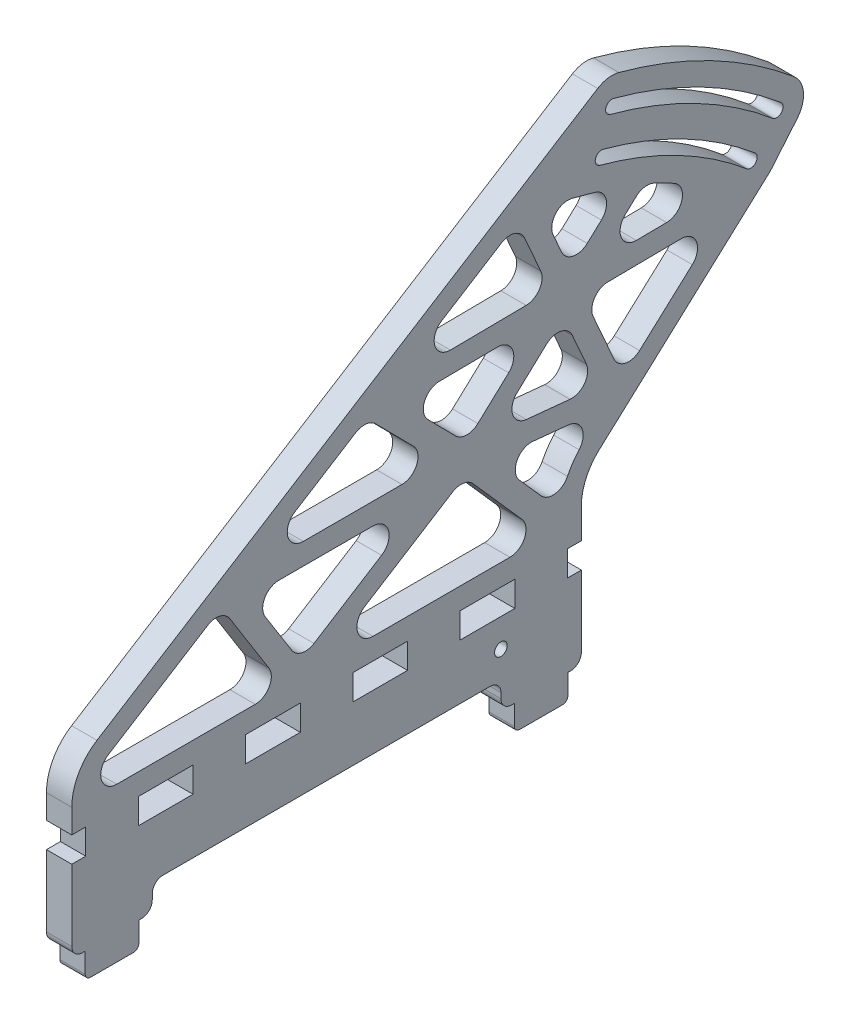
SolidWorks part; units mm, degrees
ref_plane "Front Plane" through (0, 0, 0) normal (0, 0, 1) x (1, 0, 0)
ref_plane "Top Plane" through (0, 0, 0) normal (0, 1, 0) x (1, 0, 0)
ref_plane "Right Plane" through (0, 0, 0) normal (1, 0, 0) x (0, 0, -1)
sketch "DriveBaseGeo"
  dimension "D1" = 6
  dimension "D2" = 6
  dimension "D5" = 203.2
  dimension "D8" = 25.4
  dimension "D9" = 25.4
  dimension "D6" = 9
  dimension "D7" = 9
sketch_block_instance "SlotOutline-1"
sketch_block "SlotOutline" parameters "D1"=12.7, "D2"=6
sketch_block_instance "SlotOutline-2"
sketch_block_instance "SlotOutline-3"
sketch_block_instance "SlotOutline-4"
sketch_block_instance "SlotOutline-5"
sketch_block_instance "SlotOutline-6"
sketch_block_instance "SlotOutline-7"
sketch_block_instance "SlotOutline-8"
sketch_block_instance "SlotOutline-9"
sketch_block_instance "SlotOutline-10"
sketch_block_instance "SlotOutline-11"
sketch_block_instance "SlotOutline-12"
sketch_block_instance "SlotOutline-13"
sketch_block_instance "SlotOutline-14"
sketch_block_instance "SlotOutline-15"
sketch_block_instance "SlotOutline-16"
sketch_block_instance "SlotOutline-17"
sketch_block_instance "SlotOutline-18"
sketch "Sketch2" plane through (0, 0, 0) normal (1, 0, 0) x (0, 0, -1)
  line L0 (-60.325, -47.8) -> (-60.325, -9.7)
  line L1 (-60.325, -9.7) -> (60.325, -9.7)
  line L2 (60.325, -9.7) -> (60.325, -47.8)
  line L3 (60.325, -47.8) -> (57.15, -47.8)
  line L4 (57.15, -47.8) -> (57.15, -53.8) construction
  line L5 (57.15, -53.8) -> (44.45, -53.8) construction
  line L6 (44.45, -53.8) -> (44.45, -47.8) construction
  line L7 (44.45, -47.8) -> (41.275, -47.8)
  line L8 (41.275, -47.8) -> (41.275, -41.45)
  line L9 (41.275, -41.45) -> (-41.275, -41.45)
  line L10 (-41.275, -41.45) -> (-41.275, -47.8)
  line L11 (-41.275, -47.8) -> (-44.45, -47.8)
  line L12 (-44.45, -47.8) -> (-44.45, -53.8) construction
  line L13 (-44.45, -53.8) -> (-57.15, -53.8) construction
  line L14 (-57.15, -53.8) -> (-57.15, -47.8) construction
  line L15 (-57.15, -47.8) -> (-60.325, -47.8)
  line L16 (-57.15, -47.8) -> (-44.45, -53.8) construction
  line L17 (44.45, -47.8) -> (57.15, -53.8) construction
  line L18 (57.15, -47.8) -> (44.45, -53.8) construction
  line L19 (-44.45, -47.8) -> (-57.15, -53.8) construction
  line L20 (101.6, -47.8) -> (-101.6, -47.8) construction
  line L21 (-41.275, -41.45) -> (-60.325, -41.45) construction
  line L22 (41.275, -41.45) -> (60.325, -41.45) construction
  line L23 (-60.325, -50.8) -> (-50.8, -50.8) construction
  line L24 (50.8, -50.8) -> (60.325, -50.8) construction
  line L25 (-57.15, -47.8) -> (-44.45, -47.8)
  line L26 (44.45, -47.8) -> (57.15, -47.8)
  line L27 (101.6, -22.4) -> (-101.6, -22.4) construction
  point P2 (50.8, -50.8)
  point P17 (-50.8, -50.8)
  dimension "D1" = 6.35
  dimension "D2" = 19.05
  dimension "D3" = 101.6
  dimension "D4" = 12.7
  dimension "D5" = 12.7
  dimension "D6" = 6
  dimension "D7" = 9.525
  dimension "D8" = 12.7
extrude "Mounting" add sketch "Sketch2" along normal mid plane 6
sketch "Sketch3" plane through (3, 0, 0) normal (1, 0, 0) x (0, 0, -1)
  line L0 (41.275, -35.1) -> (106.5822, 42.7301) construction
  line L3 (67.571, 63.0381) -> (41.275, -35.1) construction
  line L4 (41.275, -35.1) -> (160.1541, -35.1) construction
  line L6 (101.6, -47.8) -> (-101.6, -47.8) construction
  line L7 (60.325, -9.7) -> (60.325, -47.8) construction
  line L8 (64.1965, 68.4172) -> (-60.325, -9.7)
  line L9 (-60.325, -9.7) -> (60.325, -9.7)
  line L10 (111.4466, 38.6484) -> (105.3241, 31.3518)
  line L11 (105.3241, 31.3518) -> (100.4597, 35.4335) construction
  line L12 (104.7349, 30.7384) -> (60.325, -9.7)
  arc A0 (110.6639, 47.5945) -> (69.2145, 69.1717) centre (41.275, -35.1) ccw
  arc A1 (106.5822, 42.7301) -> (67.571, 63.0381) centre (41.275, -35.1) ccw construction
  arc A2 (107.5464, 43.8792) -> (67.9592, 64.487) centre (41.275, -35.1) ccw
  arc A3 (105.618, 41.581) -> (67.1828, 61.5892) centre (41.275, -35.1) ccw
  arc A4 (105.618, 41.581) -> (107.5464, 43.8792) centre (106.5822, 42.7301) ccw
  arc A5 (67.9592, 64.487) -> (67.1828, 61.5892) centre (67.571, 63.0381) ccw
  arc A6 (110.6639, 47.5945) -> (111.4466, 38.6484) centre (106.5822, 42.7301) cw
  arc A7 (69.2145, 69.1717) -> (64.1965, 68.4172) centre (67.571, 63.0381) ccw
  circle A8 centre (41.275, -35.1) radius 1.5
  arc A9 (100.4597, 35.4335) -> (65.1058, 53.8376) centre (41.275, -35.1) ccw construction
  arc A10 (101.4239, 36.5826) -> (65.494, 55.2865) centre (41.275, -35.1) ccw
  arc A11 (99.4955, 34.2845) -> (64.7175, 52.3887) centre (41.275, -35.1) ccw
  arc A12 (99.4955, 34.2845) -> (101.4239, 36.5826) centre (100.4597, 35.4335) ccw
  arc A13 (65.494, 55.2865) -> (64.7175, 52.3887) centre (65.1058, 53.8376) ccw
  arc A14 (105.3241, 31.3518) -> (104.7349, 30.7384) centre (100.4597, 35.4335) cw
  point P5 (88.1887, 55.0203)
  point P21 (41.275, -35.1)
  point P27 (83.7905, 46.5715)
  dimension "D1" = 3
  dimension "D4" = 6.35
  dimension "D8" = 3
  dimension "D2" = 25
  dimension "D3" = 50
  dimension "D5" = 101.6
  dimension "D6" = 12.7
  dimension "D7" = 19.05
  dimension "D9" = 9.525
extrude "Boss-Extrude2" add sketch "Sketch3" against normal up to surface (6 mm away) up to face at (-3, -36.6875, 0)
extrude "PivotHole" cut sketch "Sketch3<2>" against normal through all both and the other way through all contours A8 region at (3, -35.1, -41.275)
sketch "Sketch3<2>" plane through (3, 0, 0) normal (1, 0, 0) x (0, 0, -1) same geometry as "Sketch3"
sketch "Sketch4" plane through (0, -47.8, 0) normal (0, -1, 0) x (1, 0, 0)
  line L0 (-3, -41.275) -> (-3, -60.325) construction
  line L1 (-3, -60.325) -> (3, -60.325) construction
  line L2 (3, -60.325) -> (3, -41.275) construction
  line L3 (3, -41.275) -> (-3, -41.275) construction
  line L4 (-3, 60.325) -> (-3, 41.275) construction
  line L5 (-3, 41.275) -> (3, 41.275) construction
  line L6 (3, 41.275) -> (3, 60.325) construction
  line L7 (3, 60.325) -> (-3, 60.325) construction
  line L8 (-3, -41.275) -> (-3, -60.325) construction
  line L9 (-3, -60.325) -> (3, -60.325) construction
  line L10 (3, -60.325) -> (3, -41.275) construction
  line L11 (3, -41.275) -> (-3, -41.275) construction
  line L12 (-3, 60.325) -> (-3, 41.275) construction
  line L13 (-3, 41.275) -> (3, 41.275) construction
  line L14 (3, 41.275) -> (3, 60.325) construction
  line L15 (3, 60.325) -> (-3, 60.325) construction
  line L16 (-3, 60.325) -> (3, 41.275) construction
  line L17 (3, 60.325) -> (-3, 41.275) construction
  line L18 (-3, -41.275) -> (3, -60.325) construction
  line L19 (3, -41.275) -> (-3, -60.325) construction
  line L21 (-3, 44.45) -> (3, 44.45)
  line L22 (-3, 44.45) -> (-3, 57.15)
  line L23 (-3, 57.15) -> (3, 57.15)
  line L24 (3, 44.45) -> (3, 57.15)
  line L25 (-3, 44.45) -> (3, 57.15) construction
  line L26 (-3, 57.15) -> (3, 44.45) construction
  line L27 (-3, -57.15) -> (3, -57.15)
  line L28 (-3, -57.15) -> (-3, -44.45)
  line L29 (-3, -44.45) -> (3, -44.45)
  line L30 (3, -57.15) -> (3, -44.45)
  line L31 (-3, -57.15) -> (3, -44.45) construction
  line L32 (-3, -44.45) -> (3, -57.15) construction
  point P6 (0, -50.8)
  point P9 (0, 50.8)
  point P10 (0, 50.8)
  point P15 (0, -50.8)
  dimension "D1" = 12.7
extrude "Tab" add sketch "Sketch4" along normal blind 6
fillet "Fillet1" radius 12.7 2 edges at (0, -9.7, 60.325) (0, -9.7, -60.325)
fillet "Fillet2" radius 2.54 6 edges at (0, -47.8, -60.325) (0, -47.8, -41.275) (0, -41.45, 41.275) (0, -47.8, 41.275) (0, -47.8, 60.325) (0, -41.45, -41.275)
fillet "TabFillet" radius 1.27 4 edges at (0, -53.8, -57.15) (0, -53.8, -44.45) (0, -53.8, 44.45) (0, -53.8, 57.15)
sketch "Sketch5" plane through (3, 0, 0) normal (1, 0, 0) x (0, 0, -1)
  line L0 (101.6, -22.4) -> (-101.6, -22.4) construction
  line L1 (-82.423, -28.4) -> (-95.377, -28.4)
  line L2 (-82.423, -28.4) -> (-82.423, -22.4)
  line L3 (-82.423, -22.4) -> (-95.377, -22.4)
  line L4 (-95.377, -28.4) -> (-95.377, -22.4)
  line L5 (-82.423, -28.4) -> (-95.377, -22.4) construction
  line L6 (-82.423, -22.4) -> (-95.377, -28.4) construction
  line L7 (101.6, -28.4) -> (-101.6, -28.4) construction
  line L8 (-95.25, -28.4) -> (-82.55, -22.4) construction
  line L9 (-57.023, -28.4) -> (-69.977, -28.4)
  line L10 (-57.023, -28.4) -> (-57.023, -22.4)
  line L11 (-69.977, -28.4) -> (-69.977, -22.4)
  line L12 (-57.023, -28.4) -> (-69.977, -22.4) construction
  line L13 (-57.023, -22.4) -> (-69.977, -28.4) construction
  line L14 (-57.023, -22.4) -> (-69.977, -22.4)
  line L15 (-31.623, -28.4) -> (-44.577, -28.4)
  line L16 (-31.623, -28.4) -> (-31.623, -22.4)
  line L17 (-44.577, -28.4) -> (-44.577, -22.4)
  line L18 (-31.623, -28.4) -> (-44.577, -22.4) construction
  line L19 (-31.623, -22.4) -> (-44.577, -28.4) construction
  line L20 (-31.623, -22.4) -> (-44.577, -22.4)
  line L21 (-6.223, -28.4) -> (-19.177, -28.4)
  line L22 (-6.223, -28.4) -> (-6.223, -22.4)
  line L23 (-19.177, -28.4) -> (-19.177, -22.4)
  line L24 (-6.223, -28.4) -> (-19.177, -22.4) construction
  line L25 (-6.223, -22.4) -> (-19.177, -28.4) construction
  line L26 (-6.223, -22.4) -> (-19.177, -22.4)
  line L27 (19.177, -28.4) -> (6.223, -28.4)
  line L28 (19.177, -28.4) -> (19.177, -22.4)
  line L29 (6.223, -28.4) -> (6.223, -22.4)
  line L30 (19.177, -28.4) -> (6.223, -22.4) construction
  line L31 (19.177, -22.4) -> (6.223, -28.4) construction
  line L32 (19.177, -22.4) -> (6.223, -22.4)
  line L33 (44.577, -28.4) -> (31.623, -28.4)
  line L34 (44.577, -28.4) -> (44.577, -22.4)
  line L35 (31.623, -28.4) -> (31.623, -22.4)
  line L36 (44.577, -28.4) -> (31.623, -22.4) construction
  line L37 (44.577, -22.4) -> (31.623, -28.4) construction
  line L38 (44.577, -22.4) -> (31.623, -22.4)
  line L39 (69.977, -28.4) -> (57.023, -28.4)
  line L40 (69.977, -28.4) -> (69.977, -22.4)
  line L41 (57.023, -28.4) -> (57.023, -22.4)
  line L42 (69.977, -28.4) -> (57.023, -22.4) construction
  line L43 (69.977, -22.4) -> (57.023, -28.4) construction
  line L44 (69.977, -22.4) -> (57.023, -22.4)
  line L45 (95.377, -28.4) -> (82.423, -28.4)
  line L46 (95.377, -28.4) -> (95.377, -22.4)
  line L47 (82.423, -28.4) -> (82.423, -22.4)
  line L48 (95.377, -28.4) -> (82.423, -22.4) construction
  line L49 (95.377, -22.4) -> (82.423, -28.4) construction
  line L50 (95.377, -22.4) -> (82.423, -22.4)
  point P0 (-88.9, -25.4)
  point P18 (-63.5, -25.4)
  dimension "D2" = 25.4
  dimension "D3" = 12.446
  dimension "D1" = 8
extrude "Cut-Extrude2" cut sketch "Sketch5" against normal through all both and the other way through all
sketch "Sketch7" plane through (3, 0, 0) normal (1, 0, 0) x (0, 0, -1)
  line L0 (33.0261, 7.8463) -> (72.5595, 44.4656) construction
  line L1 (68.2118, 4.352) -> (47.2733, 51.8037) construction
  line L2 (11.6881, 29.4797) -> (96.2301, 30.393) construction
  line L3 (-24.948, 6.4965) -> (-7.8091, -20.8234)
  line L4 (-7.8091, -20.8234) -> (34.3778, 5.6959)
  line L5 (34.8344, 9.63) -> (17.6972, 27.0045)
  line L6 (17.6972, 27.0045) -> (96.2576, 27.8531)
  line L7 (31.122, 6.1652) -> (53.3409, -19.0011)
  line L8 (64.1304, 7.3098) -> (44.9494, 50.7783)
  line L9 (64.1304, 7.3098) -> (33.2771, 10.3739)
  line L10 (35.0518, 6.2605) -> (76.5725, 44.7206)
  line L11 (-20.6447, 9.1961) -> (-6.2079, -13.8166)
  line L12 (-6.2079, -13.8166) -> (31.6743, 9.9967)
  line L13 (31.2177, 6.0627) -> (5.679, 31.955)
  line L14 (5.679, 31.955) -> (96.2027, 32.9328)
  line L15 (34.9302, 9.5274) -> (57.1491, -15.6389)
  line L16 (72.2933, 1.3942) -> (49.5971, 52.8291)
  line L17 (72.2933, 1.3942) -> (32.7751, 5.3187)
  line L18 (31.3, 9.7097) -> (70.8334, 46.329)
  line L19 (-22.7963, 5.3063) -> (33.0261, 5.3063)
  line L20 (-22.7963, 10.3863) -> (33.0261, 10.3863)
  line L21 (34.7521, 5.9829) -> (74.2855, 42.6021) construction
  line L26 (-55.245, -17.32) -> (55.245, -17.32)
  line L27 (96.2301, 30.393) -> (96.4931, 30.1041)
  line L28 (63.4027, 47.4818) -> (47.2733, 51.8037)
  line L29 (-22.7963, 7.8463) -> (-7.0085, -17.32) construction
  line L30 (-7.0085, -17.32) -> (33.0261, 7.8463) construction
  line L31 (33.0261, 7.8463) -> (55.245, -17.32) construction
  line L32 (-22.7963, 7.8463) -> (33.0261, 7.8463) construction
  line L34 (33.0261, 7.8463) -> (11.6881, 29.4797) construction
  line L37 (68.2118, 4.352) -> (33.0261, 7.8463) construction
  line L52 (-55.245, -16.725) -> (-55.245, -17.32)
  line L53 (-55.245, -17.32) -> (-51.943, -17.32)
  line L54 (-51.943, -17.32) -> (-51.943, -33.48)
  line L55 (-51.943, -33.48) -> (-55.245, -33.48)
  line L56 (-55.245, -33.48) -> (-55.245, -42.72)
  line L57 (-55.245, -42.72) -> (-52.07, -42.72)
  line L58 (-52.07, -42.72) -> (-52.07, -48.72)
  line L59 (-52.07, -48.72) -> (-49.53, -48.72)
  line L60 (-49.53, -48.72) -> (-49.53, -42.72)
  line L61 (-49.53, -42.72) -> (-46.2484, -42.72)
  line L62 (-38.735, -36.37) -> (38.735, -36.37)
  line L63 (46.2484, -42.72) -> (49.53, -42.72)
  line L64 (49.53, -42.72) -> (49.53, -48.72)
  line L65 (49.53, -48.72) -> (52.07, -48.72)
  line L66 (52.07, -48.72) -> (52.07, -42.72)
  line L67 (52.07, -42.72) -> (55.245, -42.72)
  line L68 (55.245, -42.72) -> (55.245, -33.48)
  line L69 (55.245, -33.48) -> (51.943, -33.48)
  line L70 (51.943, -33.48) -> (51.943, -17.32)
  line L71 (51.943, -17.32) -> (55.245, -17.32)
  line L72 (55.245, -17.32) -> (55.245, -15.312)
  line L73 (61.0542, -2.1655) -> (101.3147, 34.4945)
  line L74 (101.4325, 34.6172) -> (107.5551, 41.9138)
  line L75 (66.8961, 64.1139) -> (-51.6744, -10.2701)
  line L76 (-55.245, -16.725) -> (-55.245, -17.32)
  line L96 (55.245, -17.32) -> (55.245, -15.312)
  line L97 (61.0542, -2.1655) -> (101.3147, 34.4945)
  line L98 (101.4325, 34.6172) -> (107.5551, 41.9138)
  line L99 (66.8961, 64.1139) -> (-51.6744, -10.2701)
  arc A19 (96.2301, 30.393) -> (63.4027, 47.4818) centre (41.275, -35.1) ccw
  arc A20 (96.2301, 30.393) -> (63.4027, 47.4818) centre (41.275, -35.1) ccw
  arc A32 (-38.735, -36.37) -> (-46.2484, -42.72) centre (-38.735, -43.99) ccw
  arc A33 (46.2484, -42.72) -> (38.735, -36.37) centre (38.735, -43.99) ccw
  arc A34 (61.0542, -2.1655) -> (55.245, -15.312) centre (73.025, -15.312) ccw
  arc A35 (101.3147, 34.4945) -> (101.4325, 34.6172) centre (100.4597, 35.4335) ccw
  arc A36 (107.5551, 41.9138) -> (107.3986, 43.703) centre (106.5822, 42.7301) ccw
  arc A37 (107.3986, 43.703) -> (67.8997, 64.2648) centre (41.275, -35.1) ccw
  arc A38 (67.8997, 64.2648) -> (66.8961, 64.1139) centre (67.571, 63.0381) ccw
  arc A39 (-51.6744, -10.2701) -> (-55.245, -16.725) centre (-47.625, -16.725) ccw
  arc A42 (61.0542, -2.1655) -> (55.245, -15.312) centre (73.025, -15.312) ccw
  arc A43 (101.3147, 34.4945) -> (101.4325, 34.6172) centre (100.4597, 35.4335) ccw
  arc A44 (107.5551, 41.9138) -> (107.3986, 43.703) centre (106.5822, 42.7301) ccw
  arc A45 (107.3986, 43.703) -> (67.8997, 64.2648) centre (41.275, -35.1) ccw
  arc A46 (67.8997, 64.2648) -> (66.8961, 64.1139) centre (67.571, 63.0381) ccw
  arc A47 (-51.6744, -10.2701) -> (-55.245, -16.725) centre (-47.625, -16.725) ccw
  point P5 (0, 0)
  point P14 (68.5414, 4.6521)
  point P17 (56.9084, 29.9682)
  point P53 (77.9806, 44.5178)
  dimension "D3" = 5.08
  dimension "D4" = 5.08
extrude "Cut-Extrude3" cut sketch "Sketch7" against normal through all both and the other way through all contours L99 A47 L76 L26 L3 | L4 L26 L7 | L13 L99 L20 | L5 L18 L6 | L10 L9 L8 | L19 L11 L12 | A42 L97 L17 L15 | L16 L97 L6 | L8 L99 L14 | L18 A20 L28 L16 | L14 A20 L10 region at (3, -9.1731, 31.7599) region at (3, -10.0309, -27.3905) region at (3, -1.068, 0.0665) region at (3, 16.2899, -5.8966) region at (3, 38.3235, -37.9789) region at (3, -1.8368, -52.6488) region at (3, 21.9147, -33.7183) region at (3, 14.2704, -53.0144) region at (3, 20.4847, -74.9912) region at (3, 43.6194, -59.4101) region at (3, 36.4019, -77.6052)
fillet "Fillet4" radius 3.81 33 edges at (0, 32.8993, -93.0968) (0, 43.3993, -75.1461) (0, 32.5792, -63.4649) (0, 45.4616, -69.897) (0, 50.9601, -50.4218) (0, 34.2514, -57.7947) (0, 50.4396, -45.0989) (0, 32.0644, -15.8081) (0, 32.4665, -53.0297) (0, 6.1554, -70.1924) (0, 27.8287, -93.9942) (0, 27.47, -60.7871) (0, 2.0505, -65.6843) (0, 4.6797, -39.2101) (0, -13.5782, -55.3297) (0, 5.3063, 18.2045) (0, -13.8166, 6.2079) (0, 5.3063, -24.2128) (0, 9.8164, -38.8907) (0, 7.3098, -64.1304) (0, 25.685, -56.0221) (0, 11.3825, -33.1059) (0, 27.3572, -50.3519) (0, 27.0045, -17.6972) (0, 28.0971, -9.4841) (0, 10.3863, 18.7475) (0, 10.3863, -26.9531) (0, -17.32, 2.2359) (0, 4.5472, -32.5505) (0, -17.32, 55.245) (0, -17.32, 10.007) (0, 6.4965, 24.948) (0, -17.32, -51.8567)
equation "\"SlotPitch\"=1"
equation "\"D8@DriveBaseGeo\" = \"SlotPitch\""
equation "\"D9@DriveBaseGeo\" = \"SlotPitch\""
equation "\"D4@Sketch7\"=\"D3@Sketch7\""
